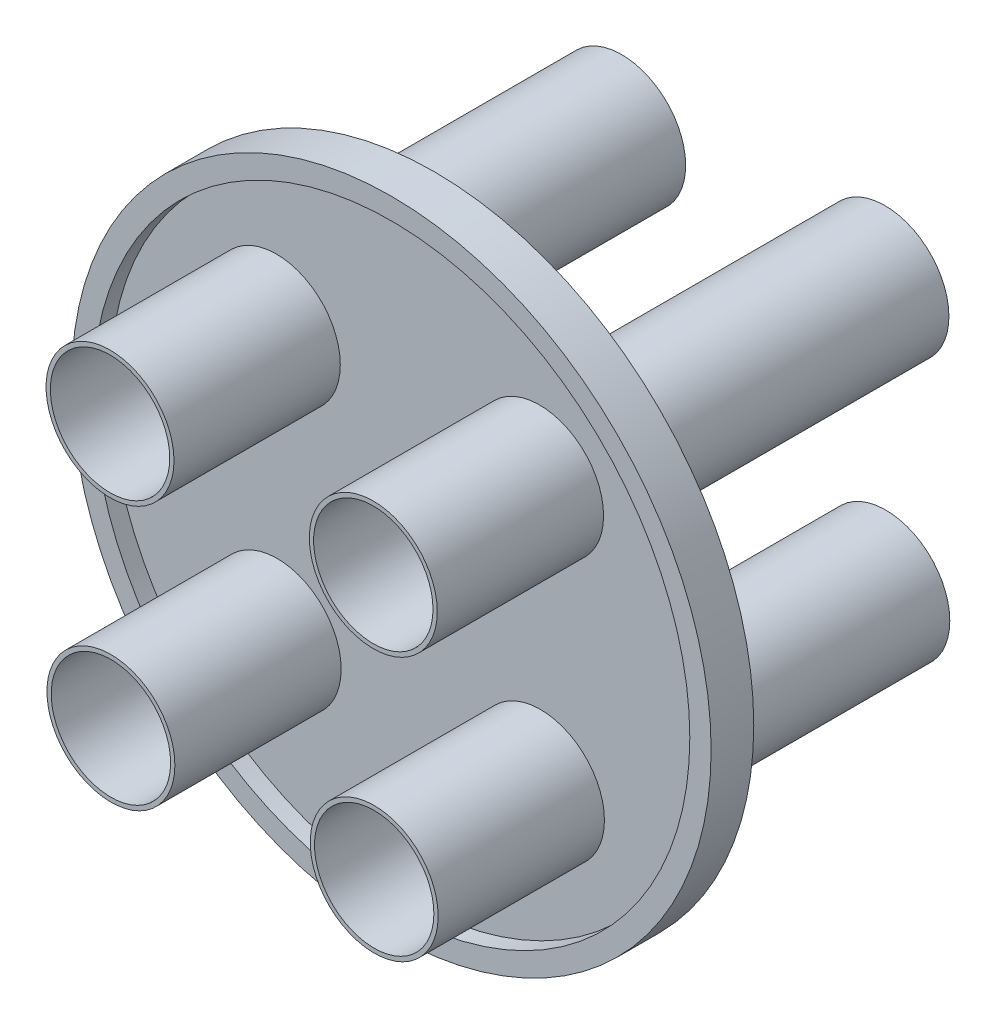
SolidWorks part; units mm, degrees
ref_plane "Front Plane" through (0, 0, 0) normal (0, 0, 1) x (1, 0, 0)
ref_plane "Top Plane" through (0, 0, 0) normal (0, 1, 0) x (1, 0, 0)
ref_plane "Right Plane" through (0, 0, 0) normal (1, 0, 0) x (0, 0, -1)
sketch "Sketch1" plane through (0, 0, 0) normal (0, 0, 1) x (1, 0, 0)
  line L0 (0, 52.3843) -> (0, -52.5574) construction
  line L1 (0, 0) -> (-37.5721, 37.3236) construction
  circle A0 centre (0, 0) radius 2.5
  circle A1 centre (0, 0) radius 35
  circle A2 centre (0, 0) radius 37.5
  circle A3 centre (-15.4872, 15.3847) radius 7.5
  circle A4 centre (15.3847, 15.4872) radius 7.5
  circle A5 centre (15.4872, -15.3847) radius 7.5
  circle A6 centre (-15.3847, -15.4872) radius 7.5
  circle A7 centre (-15.4872, 15.3847) radius 7
  circle A8 centre (15.3847, 15.4872) radius 7
  circle A9 centre (15.4872, -15.3847) radius 7
  circle A10 centre (-15.3847, -15.4872) radius 7
  point P19 (0, 0)
  point P27 (0, 0)
  dimension "D1" = 5
  dimension "D2" = 70
  dimension "D3" = 75
  dimension "D4" = 15
  dimension "D6" = 14
  dimension "D5" = 4
extrude "Boss-Extrude1" add sketch "Sketch1" along normal blind 2.5 and the other way blind 2.5 contours A2 A1 region at (-36.4393, 0, 0)
extrude "Boss-Extrude2" add sketch "Sketch1<3>" along normal blind 0.5 and the other way blind 0.5 contours A1 A6 A5 A4 A3 A0 region at (-34.0101, 0, 0)
sketch "Sketch1<3>" plane through (0, 0, 0) normal (0, 0, 1) x (1, 0, 0) same geometry as "Sketch1"
extrude "Boss-Extrude3" add sketch "Sketch1<4>" along normal blind 20 and the other way blind 40 contours A4 | A3 | A6 | A5 region at (-22.7751, 15.3847, 0) region at (8.0969, 15.4872, 0) region at (8.1993, -15.3847, 0) region at (-22.6726, -15.4872, 0)
sketch "Sketch1<4>" plane through (0, 0, 0) normal (0, 0, 1) x (1, 0, 0) same geometry as "Sketch1"
ref_plane "Plane1" through (0, 23, 0) normal (0, 1, 0) x (1, 0, 0)
sketch "Sketch2" plane through (0, 23, 0) normal (0, 1, 0) x (1, 0, 0)
  line L0 (-15.4872, -20) -> (-15.4872, -6.5656) construction
  line L1 (-22.9872, -20) -> (-7.9872, -20) construction
  line L2 (-17.9872, -20) -> (-17.9872, -2.6625)
  line L3 (-12.9872, -20) -> (-12.9872, -2.6625)
  line L4 (-17.9872, -2.6625) -> (-12.9872, -2.6625)
  line L5 (-17.9872, -20) -> (-12.9872, -20)
  dimension "D1" = 5
